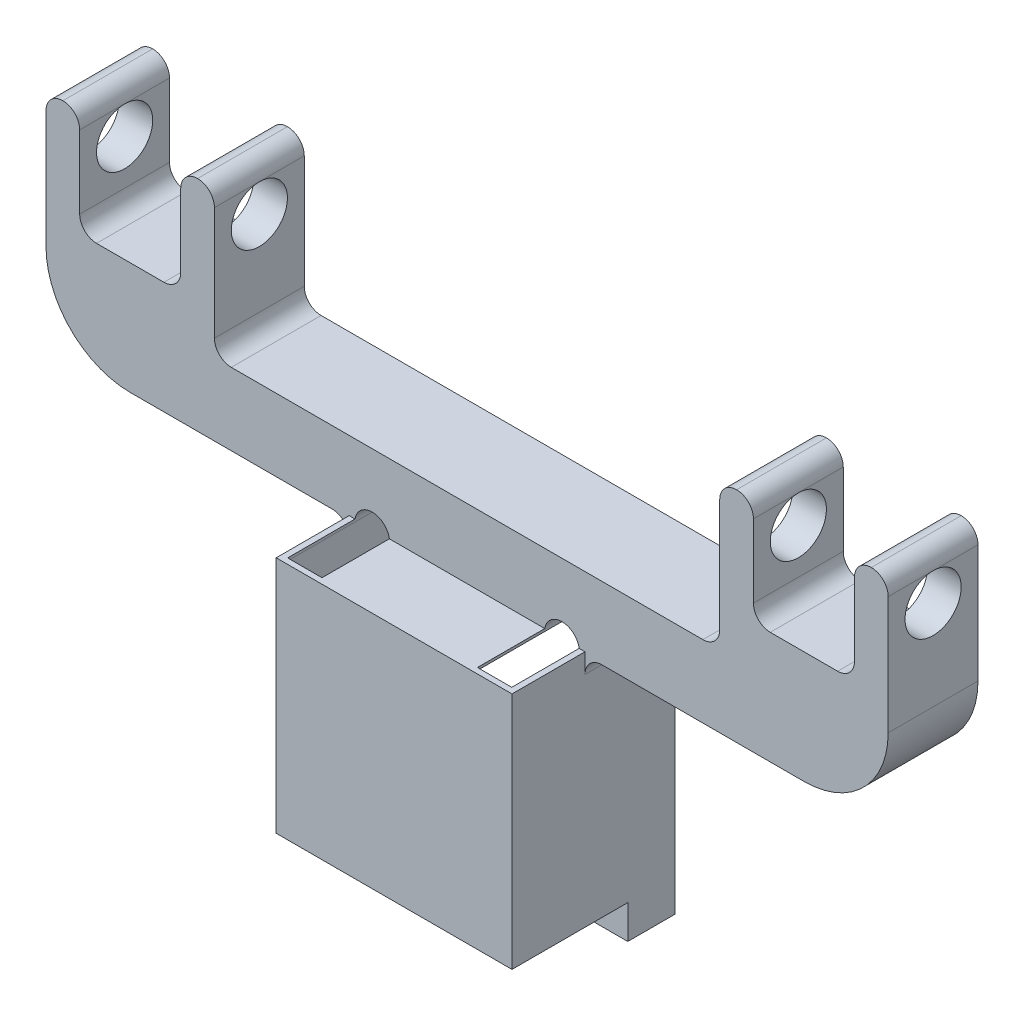
SolidWorks part; units mm, degrees
ref_plane "Plan de face" through (0, 0, 0) normal (0, 0, 1) x (1, 0, 0)
ref_plane "Plan de dessus" through (0, 0, 0) normal (0, 1, 0) x (1, 0, 0)
ref_plane "Plan de droite" through (0, 0, 0) normal (1, 0, 0) x (0, 0, -1)
sketch "Esquisse1" plane through (0, 0, 0) normal (0, 0, 1) x (1, 0, 0)
  line L1 (-75, -60) -> (75, -60)
  line L2 (-75, -60) -> (-75, 60)
  line L3 (-75, 60) -> (75, 60)
  line L4 (75, -60) -> (75, 60)
  line L5 (-75, -60) -> (75, 60) construction
  line L6 (-75, 60) -> (75, -60) construction
  point P0 (0, 0)
  dimension "D1" = 150
  dimension "D2" = 120
extrude "Boss.-Extru.1" add sketch "Esquisse1" along normal blind 29
sketch "Esquisse2" plane through (0, 0, 0) normal (0, 0, -1) x (-1, 0, 0)
  line L6 (-13.8, -12) -> (13.8, -12)
  line L7 (-20, -12) -> (-20, -52)
  line L8 (20, -12) -> (20, -52)
  line L9 (-13.8, -52) -> (13.8, -52)
  line L10 (75, -60) -> (-75, -60) construction
  line L11 (75, 60) -> (75, -60) construction
  arc A4 (20, -12) -> (13.8, -12) centre (16.9, -12) ccw
  arc A5 (13.8, -52) -> (20, -52) centre (16.9, -52) ccw
  arc A6 (-20, -12) -> (-13.8, -12) centre (-16.9, -12) cw
  arc A7 (-13.8, -52) -> (-20, -52) centre (-16.9, -52) cw
  dimension "D5" = 3.1
  dimension "D6" = 3.1
  dimension "D1" = 40
  dimension "D2" = 40
  dimension "D3" = 8
  dimension "D4" = 55
extrude "Enlèv. mat.-Extru.1" cut sketch "Esquisse2" against normal blind 28
sketch "Esquisse3" plane through (0, 0, 0) normal (0, 0, -1) x (-1, 0, 0)
  line L1 (75, -60) -> (-75, -60) construction
  line L2 (-24, -12) -> (-75, -12)
  line L3 (-75, -60) -> (-75, 60) construction
  line L4 (-75, -12) -> (-75, -60)
  line L5 (-75, -60) -> (-21, -60)
  line L8 (24, -12) -> (75, -12)
  line L9 (75, 60) -> (75, -60) construction
  line L10 (75, -12) -> (75, -60)
  line L11 (75, -60) -> (21, -60)
  line L16 (-21, -60) -> (-21, -15)
  line L17 (21, -60) -> (21, -15)
  line L18 (-20, -12) -> (-20, -52) construction
  line L19 (20, -52) -> (20, -12) construction
  line L20 (13.8, -12) -> (-13.8, -12) construction
  line L21 (13.8, -12) -> (-13.8, -12) construction
  arc A0 (-21, -15) -> (-24, -12) centre (-24, -15) ccw
  arc A1 (21, -15) -> (24, -12) centre (24, -15) cw
  point P24 (-23.7465, -11.6351)
  point P25 (-26.8916, -11.8516)
  point P26 (-21, -14.6084)
  point P27 (-21, -14.5957)
  dimension "D1" = 3
  dimension "D2" = 3
  dimension "D3" = 1
  dimension "D4" = 1
  dimension "D5" = 0
  dimension "D6" = 0
extrude "Enlèv. mat.-Extru.2" cut sketch "Esquisse3" against normal through all
sketch "Esquisse4" plane through (0, 0, 28) normal (0, 0, -1) x (-1, 0, 0)
  point P0 (-11.5526, -41)
  point P1 (11.7176, -41)
  point P2 (34.4928, -10.4799)
  point P5 (0, 0)
  point P6 (0, 0)
sketch "Esquisse5" plane through (0, 0, 0) normal (0, 0, -1) x (-1, 0, 0)
  line L0 (-45, 60) -> (45, 60)
  line L1 (-45, 60) -> (-45, 3.8748)
  line L2 (45, 60) -> (45, 3.8748)
  line L4 (-75, 60) -> (75, 60) construction
  line L5 (-75, -12) -> (-75, 60) construction
  line L6 (75, 60) -> (75, -12) construction
  line L9 (-42, 0.8748) -> (42, 0.8748)
  arc A0 (-42, 0.8748) -> (-45, 3.8748) centre (-42, 3.8748) cw
  arc A1 (42, 0.8748) -> (45, 3.8748) centre (42, 3.8748) ccw
  point P14 (-37.2968, -1.9728)
  point P15 (45, 6.3412)
  dimension "D3" = 3
  dimension "D4" = 3
  dimension "D1" = 30
  dimension "D2" = 30
extrude "Enlèv. mat.-Extru.3" cut sketch "Esquisse5" against normal through all
sketch "Esquisse6" plane through (-75, 0, 0) normal (-1, 0, 0) x (0, 0, 1)
  line L0 (0, 60) -> (0, -12) construction
  circle A0 centre (8, 19) radius 5
  dimension "D1" = 10
  dimension "D2" = 8
extrude "Enlèv. mat.-Extru.4" cut sketch "Esquisse6" against normal through all both and the other way through all
sketch "Esquisse9" plane through (-75, 0, 0) normal (-1, 0, 0) x (0, 0, 1)
  line L0 (0, 27) -> (16, 27)
  line L1 (0, 60) -> (0, -12) construction
  line L2 (16, 27) -> (16, -11.5)
  line L3 (16, -11.5) -> (29, -11.5)
  line L4 (29, 60) -> (29, -12) construction
  line L5 (29, -11.5) -> (29, 60)
  line L6 (29, 60) -> (0, 60)
  line L7 (0, 60) -> (0, 27)
  line L8 (0, -12) -> (29, -12) construction
  line L9 (29, -12) -> (0, -12) construction
  circle A0 centre (8, 19) radius 5 construction
  dimension "D3" = 8
  dimension "D1" = 1
  dimension "D2" = 8
extrude "Enlèv. mat.-Extru.6" cut sketch "Esquisse9" against normal through all both and the other way through all
sketch "Esquisse12" plane through (0, 0, 0) normal (0, 0, -1) x (-1, 0, 0)
  line L0 (-69, 27) -> (-69, 11)
  line L1 (-75, 27) -> (-45, 27) construction
  line L2 (-51, 27) -> (-51, 11)
  line L3 (-75, -12) -> (-75, 27) construction
  line L4 (-45, 27) -> (-45, 3.8748) construction
  line L5 (-66, 8) -> (-54, 8)
  line L6 (-69, 27) -> (-51, 27)
  arc A0 (-69, 11) -> (-66, 8) centre (-66, 11) ccw
  arc A1 (-51, 11) -> (-54, 8) centre (-54, 11) cw
  dimension "D3" = 3
  dimension "D4" = 3
  dimension "D1" = 6
  dimension "D2" = 6
  dimension "D5" = 19
extrude "Enlèv. mat.-Extru.8" cut sketch "Esquisse12" against normal blind 28
mirror "Symétrie1" about plane through (0, 0, 0) normal (1, 0, 0) of "Enlèv. mat.-Extru.8"
sketch "Esquisse13" plane through (0, 0, 0) normal (0, 0, -1) x (-1, 0, 0)
  line L1 (20, -52) -> (20, -12) construction
  line L3 (-20, -12) -> (-20, -52) construction
  line L4 (13.8, -12) -> (-13.8, -12) construction
  line L5 (-13.8, -52) -> (13.8, -52) construction
  circle A0 centre (-5.55, -8) radius 1.65
  circle A1 centre (5.55, -8) radius 1.65
  circle A2 centre (-6.55, -56) radius 1.65
  circle A3 centre (5.55, -56) radius 1.65
  point P1 (5.55, -8)
  point P3 (-5.55, -8)
  point P5 (-6.55, -56)
  point P6 (5.55, -56)
  dimension "D9" = 3.3
  dimension "D10" = 3.3
  dimension "D11" = 3.3
  dimension "D12" = 3.3
  dimension "D1" = 14.45
  dimension "D2" = 14.45
  dimension "D4" = 14.45
  dimension "D5" = 4
  dimension "D6" = 4
  dimension "D7" = 4
  dimension "D8" = 4
extrude "Enlèv. mat.-Extru.9" cut sketch "Esquisse13" against normal blind 10
fillet "Congé1" radius 15 1 edges at (-75, -12, 14.5)
fillet "Congé2" radius 15 1 edges at (75, -12, 14.5)
sketch "Esquisse14" plane through (-21, 0, 0) normal (-1, 0, 0) x (0, 0, 1)
  line L0 (29, -60) -> (8.3822, -60)
  line L1 (29, -60) -> (0, -60) construction
  line L2 (29, -60) -> (29, -54)
  line L3 (29, -15) -> (29, -60) construction
  line L4 (29, -54) -> (8.3822, -54)
  line L5 (8.3822, -60) -> (8.3822, -54)
  point P5 (8.3822, -54)
  point P11 (8.1334, -54)
  dimension "D2" = 6
extrude "Enlèv. mat.-Extru.10" cut sketch "Esquisse14" against normal through all
sketch "Esquisse15" plane through (0, -52, 0) normal (0, 1, 0) x (1, 0, 0)
  line L6 (-13.5, -26) -> (-13.5, -25)
  line L7 (-20, -28) -> (-20, 0) construction
  line L8 (-11.5, -28) -> (-6.5, -28)
  line L9 (13.8, -28) -> (-13.8, -28) construction
  line L10 (-4.5, -26) -> (-4.5, -25)
  line L11 (-6.5, -23) -> (-11.5, -23)
  arc A0 (-4.5, -26) -> (-6.5, -28) centre (-6.5, -26) cw
  arc A1 (-11.5, -28) -> (-13.5, -26) centre (-11.5, -26) cw
  arc A2 (-11.5, -23) -> (-13.5, -25) centre (-11.5, -25) ccw
  arc A3 (-6.5, -23) -> (-4.5, -25) centre (-6.5, -25) cw
  dimension "D4" = 2
  dimension "D5" = 2
  dimension "D6" = 2
  dimension "D7" = 2
  dimension "D1" = 6.5
  dimension "D2" = 5
  dimension "D3" = 9
extrude "Enlèv. mat.-Extru.11" cut sketch "Esquisse15" against normal blind 10
mirror "Symétrie4" about plane through (0, 0, 0) normal (1, 0, 0) of "Enlèv. mat.-Extru.11"
sketch "Esquisse16" plane through (0, 0, 0) normal (0, 0, -1) x (-1, 0, 0)
  line L1 (-13.8, -52) -> (13.8, -52) construction
  line L3 (-12, -53) -> (-7, -53)
  line L4 (-15, -50) -> (-4, -50)
  arc A0 (-15, -50) -> (-12, -53) centre (-12, -50) ccw
  arc A1 (-7, -53) -> (-4, -50) centre (-7, -50) ccw
  dimension "D4" = 3
  dimension "D5" = 3
  dimension "D1" = 1
extrude "Enlèv. mat.-Extru.14" cut sketch "Esquisse16" against normal blind 25
mirror "Symétrie5" about plane through (0, 0, 0) normal (1, 0, 0) of "Enlèv. mat.-Extru.14"
fillet "Congé6" radius 3 8 edges at (-75, 27, 8) (-69, 27, 8) (-45, 27, 8) (-51, 27, 8) (75, 27, 8) (69, 27, 8) (51, 27, 8) (45, 27, 8)
sketch "Esquisse17" plane through (0, -11.5, 0) normal (0, 1, 0) x (1, 0, 0)
  line L1 (63.8406, -16) -> (19.9594, -16) construction
  line L2 (63.8406, -16) -> (63.8406, -29)
  line L3 (63.8406, -29) -> (24.389, -29)
  line L4 (63.8406, -29) -> (-63.8406, -29) construction
  line L6 (24.389, -29) -> (24.389, -16)
  line L7 (24.389, -16) -> (63.8406, -16)
extrude "Enlèv. mat.-Extru.15" cut sketch "Esquisse17" against normal blind 22
mirror "Symétrie6" about plane through (0, 0, 0) normal (1, 0, 0) of "Enlèv. mat.-Extru.15"
sketch "Esquisse18" plane through (0, -11.5, 0) normal (0, 1, 0) x (1, 0, 0)
  line L5 (24.389, -16) -> (24.389, -29)
  line L6 (24.389, -16) -> (24.389, -29) construction
  line L8 (21, -16) -> (21, -29)
  line L9 (24.389, -29) -> (-24.389, -29) construction
  line L10 (21, -29) -> (24.389, -29)
  line L11 (24.389, -16) -> (19.9594, -16) construction
  line L12 (24.389, -16) -> (21, -16)
  line L13 (20, -28) -> (20, 0) construction
  dimension "D1" = 1
extrude "Enlèv. mat.-Extru.16" cut sketch "Esquisse18" against normal blind 22
mirror "Symétrie7" about plane through (0, 0, 0) normal (1, 0, 0) of "Enlèv. mat.-Extru.16"
